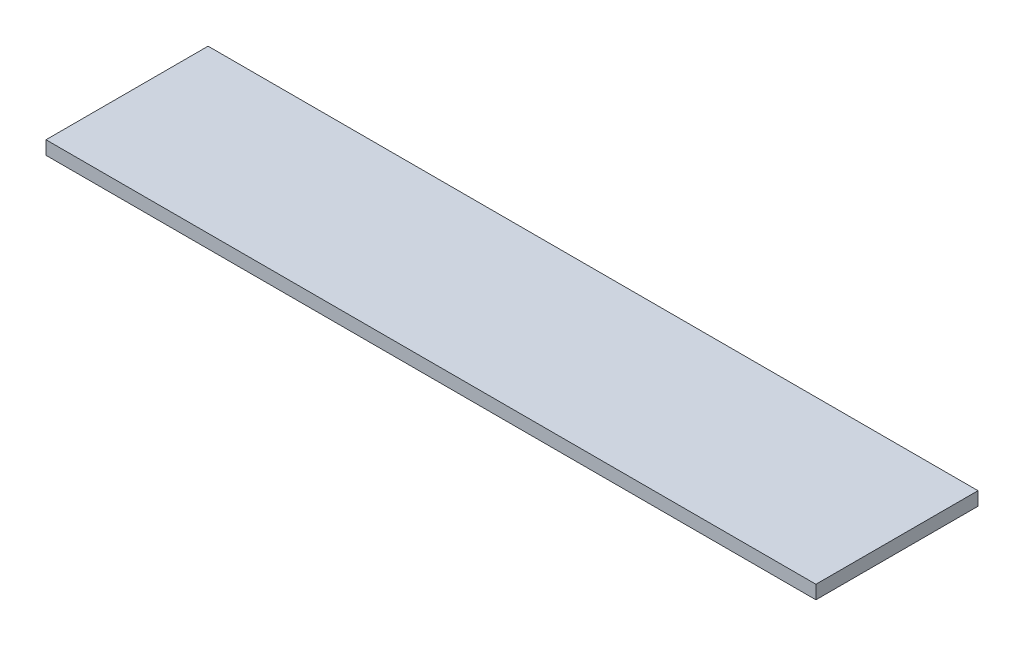
SolidWorks part; units mm, degrees
material "Cast Carbon Steel"
ref_plane "Front Plane" through (0, 0, 0) normal (0, 0, 1) x (1, 0, 0)
ref_plane "Top Plane" through (0, 0, 0) normal (0, 1, 0) x (1, 0, 0)
ref_plane "Right Plane" through (0, 0, 0) normal (1, 0, 0) x (0, 0, -1)
sketch "Sketch1" plane through (0, 0, 0) normal (0, 1, 0) x (1, 0, 0)
  line L1 (-295.5989, 185.7663) -> (428.3011, 185.7663)
  line L2 (-295.5989, 185.7663) -> (-295.5989, 33.3663)
  line L3 (-295.5989, 33.3663) -> (428.3011, 33.3663)
  line L4 (428.3011, 185.7663) -> (428.3011, 33.3663)
  dimension "D1" = 723.9
  dimension "D2" = 152.4
extrude "Boss-Extrude1" add sketch "Sketch1" along normal blind 12.7
